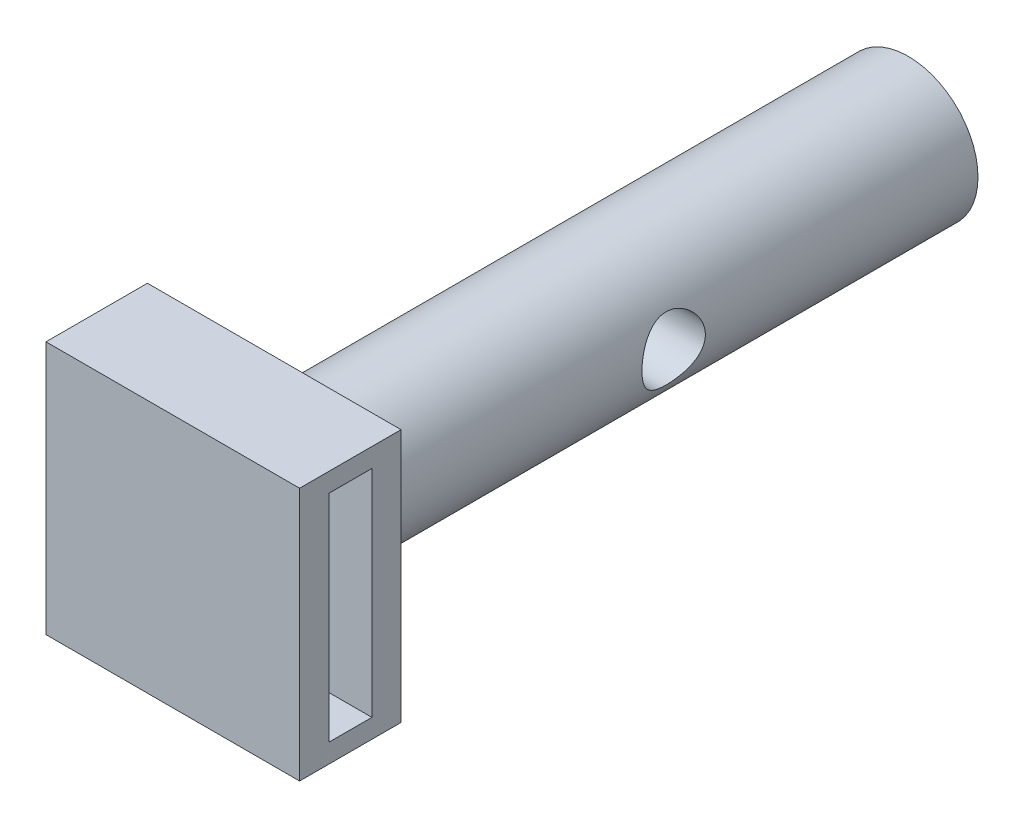
SolidWorks part; units mm, degrees
ref_plane "Front Plane" through (0, 0, 0) normal (0, 0, 1) x (1, 0, 0)
ref_plane "Top Plane" through (0, 0, 0) normal (0, 1, 0) x (1, 0, 0)
ref_plane "Right Plane" through (0, 0, 0) normal (1, 0, 0) x (0, 0, -1)
sketch "Sketch2" plane through (0, 0, 0) normal (0, 0, 1) x (1, 0, 0)
  circle A4 centre (0, 0) radius 2.75
  point P3 (25, 0)
  dimension "D1" = 5.5
ref_plane "Plane1" through (0, 0, 25) normal (0, 0, 1) x (1, 0, 0)
sketch "Sketch3" plane through (0, 0, 25) normal (0, 0, 1) x (1, 0, 0)
  line L0 (-5, 5) -> (5, 5)
  line L1 (-5, 5) -> (-5, -5)
  line L2 (-5, -5) -> (5, -5)
  line L3 (5, 5) -> (5, -5)
  circle A0 centre (0, 0) radius 2.75
  point P3 (0, 5)
  point P9 (5, 0)
  dimension "D1" = 5.5
  dimension "D2" = 10
loft "Loft1" add profiles "Sketch2", "Sketch3" connector at (0.2399, 2.7395, 0) connector at (0.0916, 2.7485, 25)
extrude "Boss-Extrude4" add sketch "Sketch3<7>" along normal blind 4 contours A0 L3 L0 L1 | A0 L1 L2 L3 | A0 | A0 L0 L1 | A0 L2 L3 region at (0, 4.8586, 25) region at (0, 0, 25)
sketch "Sketch3<7>" plane through (0, 0, 25) normal (0, 0, 1) x (1, 0, 0) same geometry as "Sketch3"
sketch "Sketch8" plane through (5, 0, 0) normal (1, 0, 0) x (0, 0, -1)
  line L0 (-29, 5) -> (-29, -5) construction
  line L1 (-27.85, 4.25) -> (-26.15, 4.25)
  line L2 (-27.85, 4.25) -> (-27.85, -4.25)
  line L3 (-27.85, -4.25) -> (-26.15, -4.25)
  line L4 (-26.15, 4.25) -> (-26.15, -4.25)
  line L5 (-29, 5) -> (-25, 5) construction
  point P4 (-27.85, 0)
  point P7 (-29, 0)
  point P8 (-27, 4.25)
  point P11 (-27, 5)
  dimension "D1" = 1.7
  dimension "D2" = 8.5
extrude "Cut-Extrude2" cut sketch "Sketch8" against normal through all both and the other way through all
fillet "Fillet1" radius 1 1 edges at (2.75, 0, 25)
ref_plane "Plane2" [suppressed] through (-3.4151, 5.9151, 0) normal (0.5, -0.866, 0) x (0, 0, -1)
ref_plane "Plane3" [suppressed] through (2.9244, -5.0652, 0) normal (0.5, -0.866, 0) x (0, 0, -1)
sketch "Sketch10" [suppressed] plane through (2.9244, -5.0652, 0) normal (0.5, -0.866, 0) x (0, 0, -1)
  line L1 (-15.5, -3.25) -> (0, -3.25) construction
  circle A0 centre (-16.5644, -7) radius 1.25
  dimension "D1" = 7
  dimension "D3" = 2.5
  dimension "D2" = 3.75
extrude "Cut-Extrude3" [suppressed] cut sketch "Sketch10" against normal blind 3 from surface contours A0
mirror "Mirror1" [suppressed] about plane through (0, 0, 0) normal (1, 0, 0)
sketch "Sketch11" plane through (0, 0, 0) normal (1, 0, 0) x (0, 0, -1)
  line L1 (0, 0) -> (-24, 0) construction
  line L2 (0, -2.75) -> (0, 2.75) construction
  line L3 (-24, -2.75) -> (-24, 2.75) construction
  circle A0 centre (-12, 0) radius 1.25
  dimension "D1" = 2.5
extrude "Cut-Extrude4" cut sketch "Sketch11" against normal through all both and the other way through all
